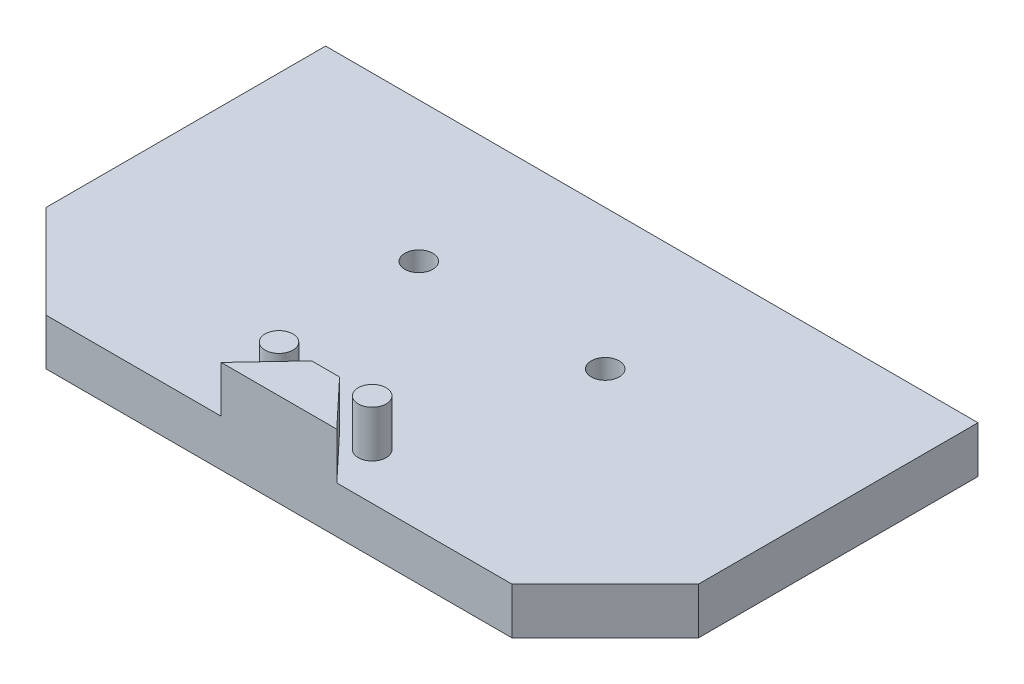
SolidWorks part; units mm, degrees
ref_plane "Front Plane" through (0, 0, 0) normal (0, 0, 1) x (1, 0, 0)
ref_plane "Top Plane" through (0, 0, 0) normal (0, 1, 0) x (1, 0, 0)
ref_plane "Right Plane" through (0, 0, 0) normal (1, 0, 0) x (0, 0, -1)
sketch "Sketch1" plane through (0, 0, 0) normal (0, 1, 0) x (1, 0, 0)
  line L1 (35, -20) -> (-35, -20)
  line L2 (35, -20) -> (35, 20)
  line L3 (35, 20) -> (-35, 20)
  line L4 (-35, -20) -> (-35, 20)
  line L5 (35, -20) -> (-35, 20) construction
  line L6 (35, 20) -> (-35, -20) construction
  point P0 (0, 0)
  dimension "D1" = 70
  dimension "D2" = 40
extrude "Boss-Extrude1" add sketch "Sketch1" along normal blind 5
sketch "Sketch2" plane through (0, 5, 0) normal (0, 1, 0) x (1, 0, 0)
  line L0 (35, 20) -> (-35, 20) construction
  line L1 (-35, 20) -> (-35, -20) construction
  line L2 (35, -20) -> (35, 20) construction
  circle A0 centre (-10, 5) radius 1.5
  circle A1 centre (10, 5) radius 1.5
  dimension "D1" = 3
  dimension "D4" = 3
  dimension "D2" = 15
  dimension "D3" = 25
  dimension "D5" = 25
  dimension "D6" = 15
extrude "Cut-Extrude1" cut sketch "Sketch2" against normal blind 5 contours A0
extrude "Cut-Extrude2" cut sketch "Sketch2<3>" against normal blind 5
sketch "Sketch2<3>" plane through (0, 5, 0) normal (0, 1, 0) x (1, 0, 0) same geometry as "Sketch2"
sketch "Sketch3" plane through (0, 5, 0) normal (0, 1, 0) x (1, 0, 0)
  line L0 (-35, -20) -> (35, -20) construction
  line L1 (-35, 20) -> (-35, -20) construction
  line L2 (35, -20) -> (35, 20) construction
  circle A0 centre (-5, -15) radius 1.5
  circle A1 centre (5, -15) radius 1.5
  dimension "D1" = 3
  dimension "D4" = 3
  dimension "D2" = 5
  dimension "D3" = 30
  dimension "D5" = 30
  dimension "D6" = 5
extrude "Boss-Extrude2" add sketch "Sketch3" along normal blind 5 contours A0
extrude "Boss-Extrude3" add sketch "Sketch3<3>" along normal blind 5
sketch "Sketch3<3>" plane through (0, 5, 0) normal (0, 1, 0) x (1, 0, 0) same geometry as "Sketch3"
ref_plane "Plane1" through (0, 0, 15) normal (0, 0, 1) x (1, 0, 0)
sketch "Sketch8" plane through (0, 5, 0) normal (0, 1, 0) x (1, 0, 0)
  line L0 (-25, -20) -> (-35, -10)
  line L1 (-35, -20) -> (35, -20) construction
  line L2 (-35, 20) -> (-35, -20) construction
  line L3 (-35, -10) -> (-35, -20)
  line L4 (-35, -20) -> (-25, -20)
  dimension "D1" = 10
  dimension "D2" = 10
extrude "Cut-Extrude3" cut sketch "Sketch8" against normal blind 10
sketch "Sketch9" plane through (0, 5, 0) normal (0, 1, 0) x (1, 0, 0)
  line L0 (35, -20) -> (25, -20)
  line L1 (-25, -20) -> (35, -20) construction
  line L2 (25, -20) -> (35, -10)
  line L3 (35, -20) -> (35, 20) construction
  line L4 (35, -10) -> (35, -20)
  dimension "D1" = 10
  dimension "D2" = 10
extrude "Cut-Extrude4" cut sketch "Sketch9" against normal blind 10
sketch "Sketch11" plane through (0, 5, 0) normal (0, 1, 0) x (1, 0, 0)
  line L0 (-25, -20) -> (25, -20) construction
  line L1 (-14.372, -15) -> (14.372, -15) construction
  line L2 (35, -10) -> (35, 20) construction
  point P0 (-6.2, -20)
  point P1 (0, -15)
  point P4 (-1.5, -15)
  point P7 (1.5, -15)
  dimension "D1" = 1.5
  dimension "D2" = 35
  dimension "D3" = 1.5
  dimension "D4" = 41.2
sketch "Sketch12" plane through (0, 5, 0) normal (0, 1, 0) x (1, 0, 0)
  line L0 (-25, -20) -> (25, -20) construction
  line L1 (35, -10) -> (35, 20) construction
  point P0 (6.2, -20)
  dimension "D1" = 28.8
sketch "Sketch13" plane through (0, 5, 0) normal (0, 1, 0) x (1, 0, 0)
  line L0 (-6.2, -20) -> (6.2, -20)
  line L1 (6.2, -20) -> (1.5, -15)
  line L2 (1.5, -15) -> (-1.5, -15)
  line L3 (-1.5, -15) -> (-6.2, -20)
extrude "Boss-Extrude4" add sketch "Sketch13" along normal blind 5
